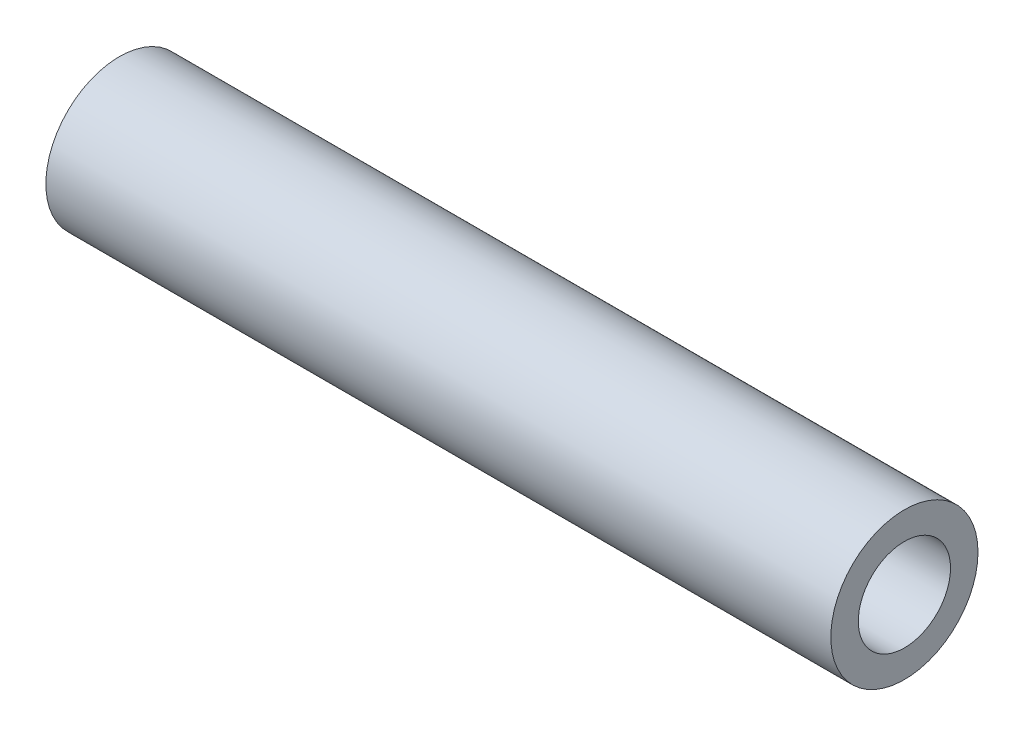
SolidWorks part; units mm, degrees
material "6061-T6 (SS)"
ref_plane "Front" through (0, 0, 0) normal (0, 0, 1) x (1, 0, 0)
ref_plane "Top" through (0, 0, 0) normal (0, 1, 0) x (1, 0, 0)
ref_plane "Right" through (0, 0, 0) normal (1, 0, 0) x (0, 0, -1)
sketch "Sketch1" plane through (0, 0, 0) normal (1, 0, 0) x (0, 0, -1)
  circle A0 centre (0, 0) radius 2.9845
  circle A1 centre (0, 0) radius 4.7625
  dimension "D1" = 9.525
  dimension "D2" = 5.969
extrude "Boss-Extrude1" add sketch "Sketch1" along normal blind 50.8
